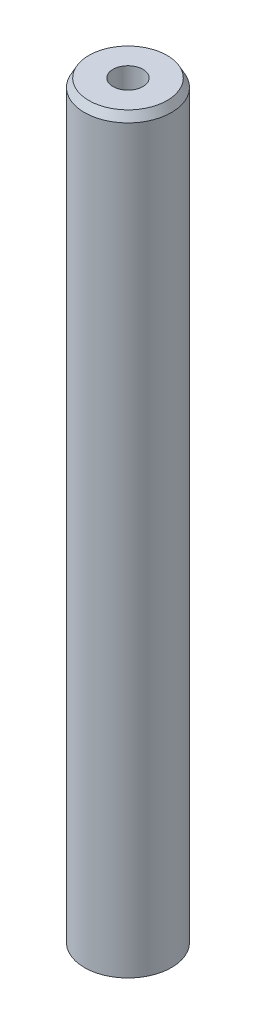
SolidWorks part; units mm, degrees
ref_plane "Front Plane" through (0, 0, 0) normal (0, 0, 1) x (1, 0, 0)
ref_plane "Top Plane" through (0, 0, 0) normal (0, 1, 0) x (1, 0, 0)
ref_plane "Right Plane" through (0, 0, 0) normal (1, 0, 0) x (0, 0, -1)
sketch "Sketch1" plane through (0, 0, 0) normal (0, 1, 0) x (1, 0, 0)
  circle A0 centre (0, 0) radius 15
  dimension "SHAFT_OD" = 30
extrude "Boss-Extrude1" add sketch "Sketch1" along normal blind 259.5228
sketch "Sketch2" plane through (0, 0, 0) normal (0, 1, 0) x (1, 0, 0)
  circle A0 centre (0, 0) radius 5.1655
  dimension "BORE_D" = 10.3311
extrude "Cut-Extrude1" cut sketch "Sketch2" along normal through all
chamfer "Chamfer1" distance 2.8217 angle 28.277 2 edges at (0, 259.5228, 15) (0, 0, 15) first distance on face at (0, 259.5228, 15) first distance on face at (0, 0, 5.1655)
